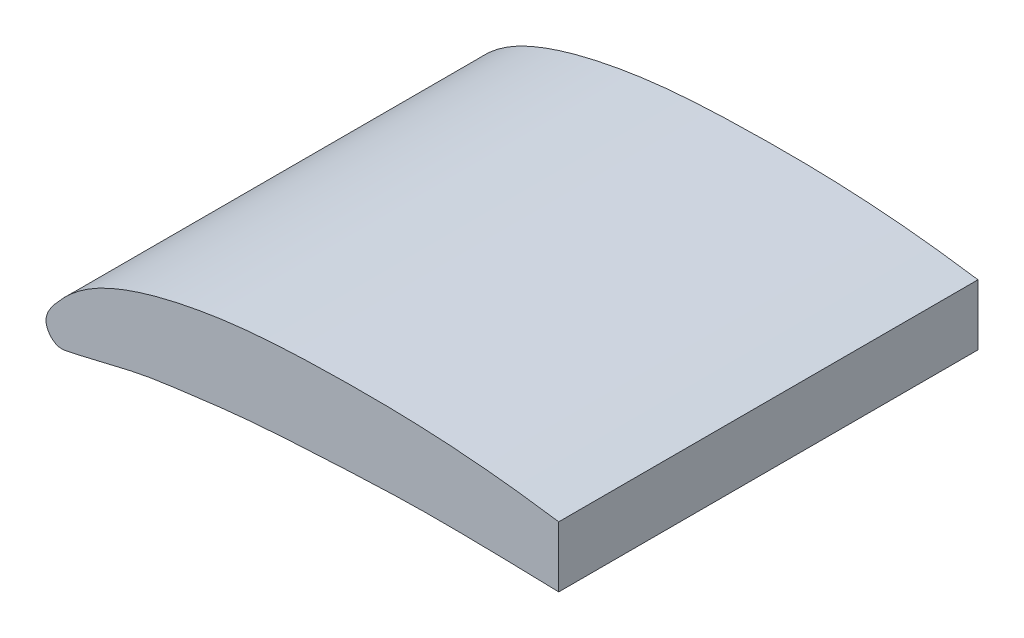
SolidWorks part; units mm, degrees
ref_plane "Front Plane" through (0, 0, 0) normal (0, 0, 1) x (1, 0, 0)
ref_plane "Top Plane" through (0, 0, 0) normal (0, 1, 0) x (1, 0, 0)
ref_plane "Right Plane" through (0, 0, 0) normal (1, 0, 0) x (0, 0, -1)
curve "Curve1"
  spline degree 3 poles (25.4, 0.0889, 0) (24.9755, 0.1879, 0) (24.1284, 0.3854, 0) (22.4316, 0.7474, 0) (20.3056, 1.1527, 0) (17.7661, 1.6728, 0) (15.2225, 2.1285, 0) (12.6828, 2.5208, 0) (10.1333, 2.7153, 0) (7.5886, 2.7177, 0) (5.4641, 2.6194, 0) (3.7724, 2.3478, 0) (2.7142, 2.0863, 0) (1.8702, 1.7836, 0) (1.2225, 1.4719, 0) (0.6864, 1.0854, 0) (0.2512, 0.6226, 0) (-0.1733, 0.0898, 0) (0.2557, -0.4257, 0) (0.7562, -0.3188, 0) (1.2698, -0.1979, 0) (1.905, -0.0426, 0) (2.7433, 0.1487, 0) (3.8055, 0.2872, 0) (5.4925, 0.5064, 0) (7.6119, 0.6227, 0) (10.1512, 0.7472, 0) (12.6929, 0.6952, 0) (15.2354, 0.6324, 0) (17.7755, 0.4534, 0) (20.3173, 0.2785, 0) (22.4335, 0.1017, 0) (24.1313, 0.0327, 0) (24.9769, -0.0484, 0) (25.4, -0.0889, 0) knots 0 0 0 0 0.025045 0.049982 0.099693 0.149405 0.198931 0.248178 0.297011 0.345669 0.394384 0.418982 0.444018 0.456913 0.470405 0.485361 0.494029 0.508284 0.517562 0.523649 0.536105 0.548579 0.561002 0.585562 0.610033 0.658766 0.707435 0.756094 0.804785 0.853571 0.902386 0.951201 0.975578 1 1 1 1
sketch "Sketch1" plane through (0, 0, 0) normal (0, 0, 1) x (1, 0, 0)
  line L0 (25.4, 0.0889) -> (25.4, -0.0889) construction
  line L1 (254, 0.889) -> (254, -0.889)
  line L2 (0, 0) -> (254, 0) construction
  line L3 (127, 0) -> (127, 24.8566) construction
  line L4 (139.7, 0) -> (139.7, 6.6099) construction
  line L5 (139.7, 6.6099) -> (139.7, 23.1662)
  line L6 (50.8, 0) -> (50.8, 4.4198) construction
  line L7 (50.8, 4.4198) -> (50.8, 25.402) construction
  line L8 (101.6, 0) -> (101.6, 7.1792) construction
  line L9 (101.6, 7.1792) -> (101.6, 26.8232) construction
  line L10 (147.4927, 0) -> (147.4927, 6.3416) construction
  line L11 (147.4927, 6.3416) -> (147.4927, 21.9573) construction
  circle A0 centre (50.8, 14.9109) radius 7.9375
  circle A1 centre (101.6, 17.0012) radius 7.9375
  circle A2 centre (147.4927, 14.1494) radius 2.2522
  spline S0 degree 3 poles (801.0896, 2896.6153) (93.9918, -50.1126) (62.4745, -7.7955) (22.4316, 0.7474) (20.3056, 1.1527) (17.7661, 1.6728) (15.2225, 2.1285) (12.6828, 2.5208) (10.1333, 2.7153) (7.5886, 2.7177) (5.4641, 2.6194) (3.7724, 2.3478) (2.7142, 2.0863) (1.8702, 1.7836) (1.2225, 1.4719) (0.6864, 1.0854) (0.2512, 0.6226) (-0.1733, 0.0898) (0.2557, -0.4257) (0.7562, -0.3188) (1.2698, -0.1979) (1.905, -0.0426) (2.7433, 0.1487) (3.8055, 0.2872) (5.4925, 0.5064) (7.6119, 0.6227) (10.1512, 0.7472) (12.6929, 0.6952) (15.2354, 0.6324) (17.7755, 0.4534) (20.3173, 0.2785) (22.4335, 0.1017) (51.136, -1.0652) (75.492, -52.2811) (315.1102, 2985.1217) knots -2.25291 -2.25291 -2.25291 -2.25291 0.025045 0.049982 0.099693 0.149405 0.198931 0.248178 0.297011 0.345669 0.394384 0.418982 0.444018 0.456913 0.470405 0.485361 0.494029 0.508284 0.517562 0.523649 0.536105 0.548579 0.561002 0.585562 0.610033 0.658766 0.707435 0.756094 0.804785 0.853571 0.902386 0.951201 0.975578 2.552608 2.552608 2.552608 2.552608 only from (25.4, 0.0889) to (25.4, -0.0889) construction
  spline S1 degree 3 poles (25.4, 0.0889) (24.9755, 0.1879) (24.1284, 0.3854) (22.4316, 0.7474) (20.3056, 1.1527) (17.7661, 1.6728) (15.2225, 2.1285) (12.6828, 2.5208) (10.1333, 2.7153) (7.5886, 2.7177) (5.4641, 2.6194) (3.7724, 2.3478) (2.7142, 2.0863) (1.8702, 1.7836) (1.2225, 1.4719) (0.6864, 1.0854) (0.2512, 0.6226) (-0.1733, 0.0898) (0.2557, -0.4257) (0.7562, -0.3188) (1.2698, -0.1979) (1.905, -0.0426) (2.7433, 0.1487) (3.8055, 0.2872) (5.4925, 0.5064) (7.6119, 0.6227) (10.1512, 0.7472) (12.6929, 0.6952) (15.2354, 0.6324) (17.7755, 0.4534) (20.3173, 0.2785) (22.4335, 0.1017) (24.1313, 0.0327) (24.9769, -0.0484) (25.4, -0.0889) knots 0 0 0 0 0.025045 0.049982 0.099693 0.149405 0.198931 0.248178 0.297011 0.345669 0.394384 0.418982 0.444018 0.456913 0.470405 0.485361 0.494029 0.508284 0.517562 0.523649 0.536105 0.548579 0.561002 0.585562 0.610033 0.658766 0.707435 0.756094 0.804785 0.853571 0.902386 0.951201 0.975578 1 1 1 1 construction
  spline S2 degree 3 poles (254, 0.889) (249.7553, 1.8786) (241.2842, 3.8535) (224.3158, 7.4736) (203.0565, 11.5272) (177.6613, 16.7283) (152.2253, 21.2846) (126.8284, 25.208) (101.3332, 27.1529) (75.8856, 27.1773) (54.6411, 26.1945) (37.7241, 23.4783) (27.1418, 20.8628) (18.7017, 17.8364) (12.2246, 14.7192) (6.8643, 10.8535) (2.5124, 6.2258) (-1.7329, 0.8975) (2.5571, -4.257) (7.5624, -3.188) (12.6982, -1.9788) (19.0498, -0.4259) (27.4332, 1.4865) (38.0551, 2.8725) (54.9249, 5.0635) (76.1187, 6.227) (101.5119, 7.4722) (126.9288, 6.9519) (152.354, 6.3244) (177.755, 4.534) (203.1733, 2.7851) (224.3353, 1.0168) (241.3134, 0.3266) (249.7685, -0.4836) (254, -0.889) knots 0 0 0 0 0.025045 0.049982 0.099693 0.149405 0.198931 0.248178 0.297011 0.345669 0.394384 0.418982 0.444018 0.456913 0.470405 0.485361 0.494029 0.508284 0.517562 0.523649 0.536105 0.548579 0.561002 0.585562 0.610033 0.658766 0.707435 0.756094 0.804785 0.853571 0.902386 0.951201 0.975578 1 1 1 1
  point P9 (139.7, 0)
  point P12 (50.8, 0)
  point P19 (50.8, 22.8484)
  point P20 (50.8, 6.9734)
  point P21 (101.6, 0)
  point P27 (147.4927, 0)
  dimension "D5" = 15.875
  dimension "D7" = 15.875
  dimension "D1" = 254
  dimension "D2" = 24.8566
  dimension "D3" = 139.7
  dimension "D4" = 50.8
  dimension "D6" = 50.8
  dimension "D8" = 147.4927
extrude "Boss-Extrude1" add sketch "Sketch1" along normal blind 114.3 contours L5 S2 | A0 | A1 region at (70.4556, 14.021, 0) region at (50.8, 14.9109, 0) region at (101.6, 17.0012, 0)
